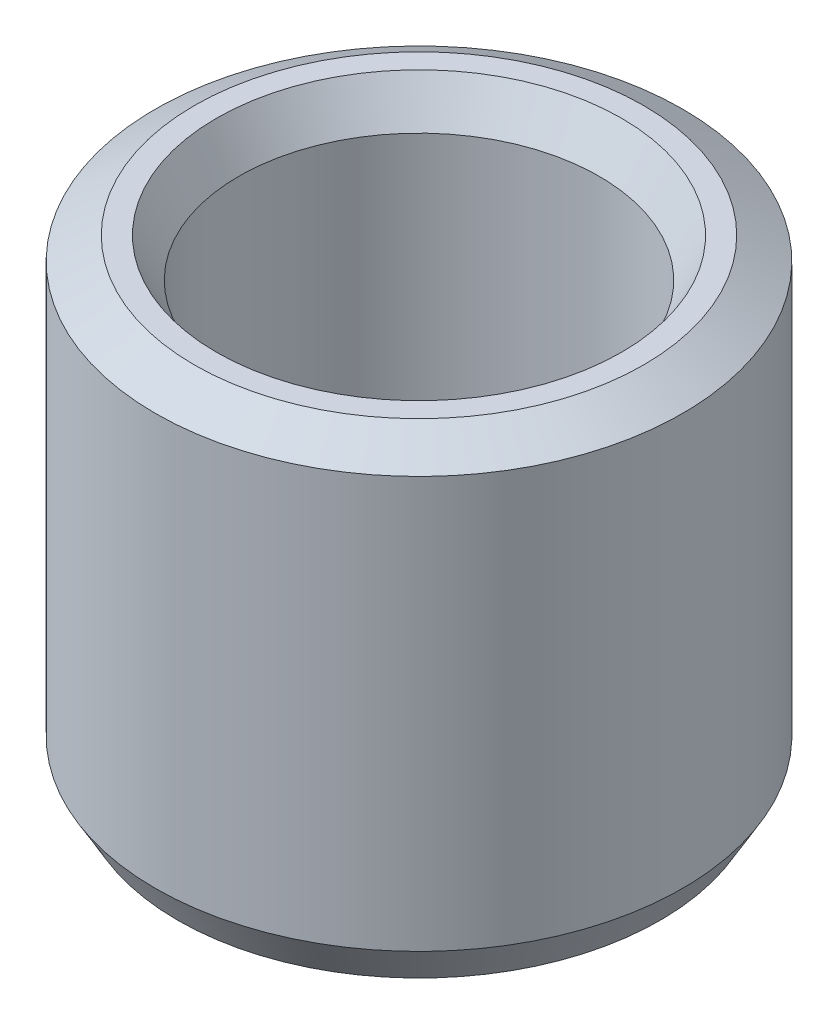
SolidWorks part; units mm, degrees
ref_plane "Front Plane" through (0, 0, 0) normal (0, 0, 1) x (1, 0, 0)
ref_plane "Top Plane" through (0, 0, 0) normal (0, 1, 0) x (1, 0, 0)
ref_plane "Right Plane" through (0, 0, 0) normal (1, 0, 0) x (0, 0, -1)
sketch "Sketch1" plane through (0, 0, 0) normal (0, 1, 0) x (1, 0, 0)
  circle A0 centre (0, 0) radius 37.5
  dimension "SLEEVE_OD" = 75
extrude "Boss-Extrude1" add sketch "Sketch1" along normal blind 67.2548
sketch "Sketch2" plane through (0, 0, 0) normal (0, 1, 0) x (1, 0, 0)
  circle A0 centre (0, 0) radius 25.6261
  dimension "BORE_D" = 51.2521
extrude "Cut-Extrude1" cut sketch "Sketch2" along normal through all
chamfer "Chamfer1" distance 3.1994 angle 60 4 edges at (0, 67.2548, 25.6261) (0, 0, 25.6261) (0, 0, 37.5) (0, 67.2548, 37.5) first distance on face at (0, 67.2548, 25.6261) first distance on face at (0, 0, 25.6261) first distance on face at (0, 67.2548, 37.5)
